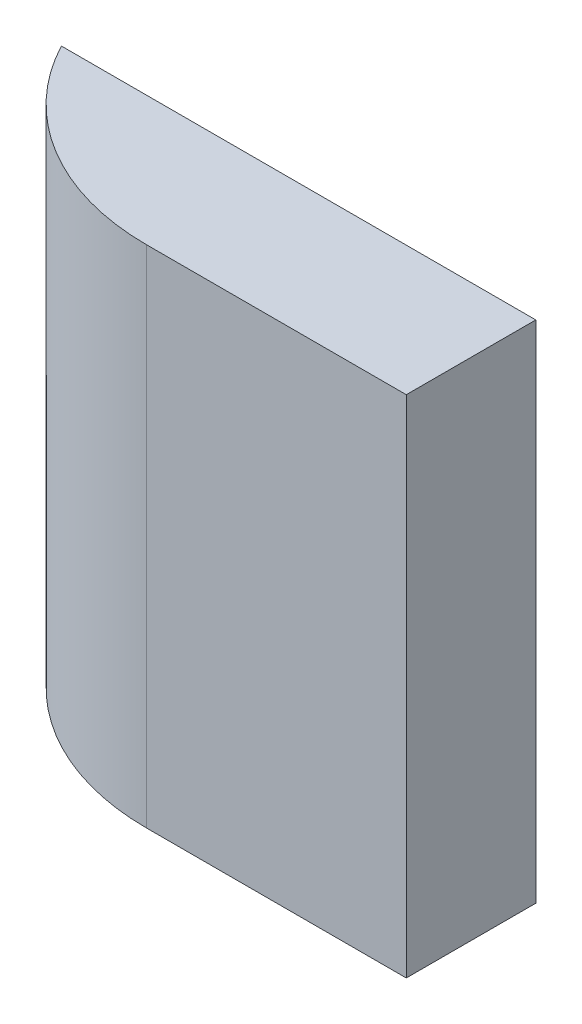
SolidWorks part; units mm, degrees
ref_plane "Front Plane" through (0, 0, 0) normal (0, 0, 1) x (1, 0, 0)
ref_plane "Top Plane" through (0, 0, 0) normal (0, 1, 0) x (1, 0, 0)
ref_plane "Right Plane" through (0, 0, 0) normal (1, 0, 0) x (0, 0, -1)
sketch "Sketch1" plane through (0, 0, 0) normal (0, 0, 1) x (1, 0, 0)
  line L0 (45.3286, -2) -> (120.3286, -2) construction
  line L1 (-101.1813, -2) -> (120.3286, -2) construction
  line L3 (45.3286, -2) -> (-101.1813, -2)
  line L4 (45.3286, -2) -> (45.3286, -158)
  line L5 (45.3286, -158) -> (-101.1813, -158)
  line L6 (-101.1813, -2) -> (-101.1813, -158)
extrude "Boss-Extrude1" add sketch "Sketch1" along normal blind 40
fillet "Fillet1" radius 75 1 edges at (-101.1813, -80, 40)
